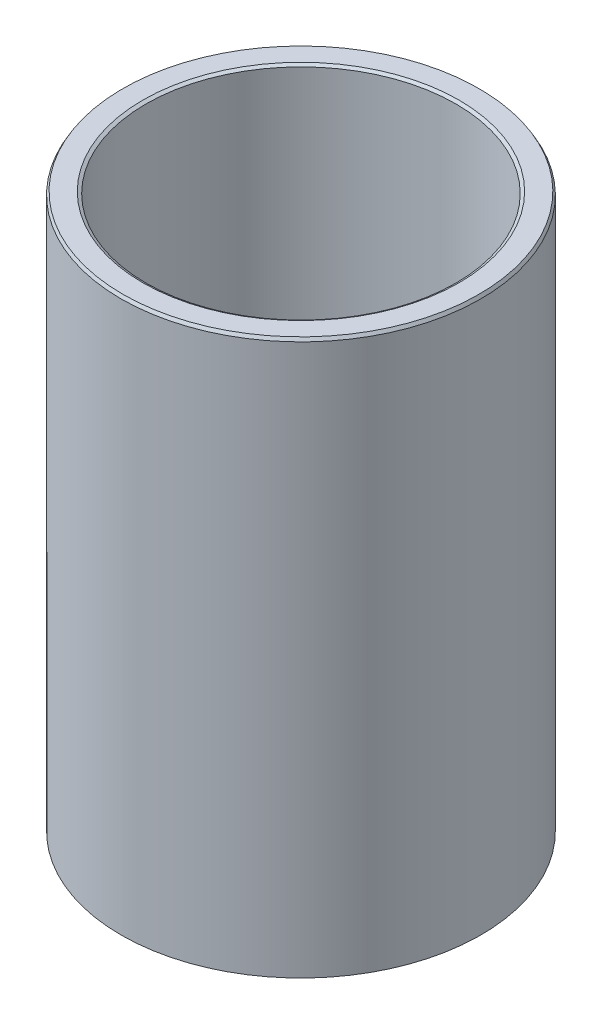
SolidWorks part; units mm, degrees
ref_plane "Front Plane" through (0, 0, 0) normal (0, 0, 1) x (1, 0, 0)
ref_plane "Top Plane" through (0, 0, 0) normal (0, 1, 0) x (1, 0, 0)
ref_plane "Right Plane" through (0, 0, 0) normal (1, 0, 0) x (0, 0, -1)
sketch "Sketch1" plane through (0, 0, 0) normal (0, 1, 0) x (1, 0, 0)
  circle A0 centre (0, 0) radius 42.5
  dimension "SLEEVE_OD" = 85
extrude "Boss-Extrude1" add sketch "Sketch1" along normal blind 131.2985
sketch "Sketch2" plane through (0, 0, 0) normal (0, 1, 0) x (1, 0, 0)
  circle A0 centre (0, 0) radius 36.6334
  dimension "BORE_D" = 73.2668
extrude "Cut-Extrude1" cut sketch "Sketch2" along normal through all
chamfer "Chamfer1" distance 0.7307 angle 30 4 edges at (0, 131.2985, 36.6334) (0, 0, 36.6334) (0, 0, 42.5) (0, 131.2985, 42.5) first distance on face at (0, 131.2985, 36.6334) first distance on face at (0, 0, 36.6334) first distance on face at (0, 131.2985, 42.5)
